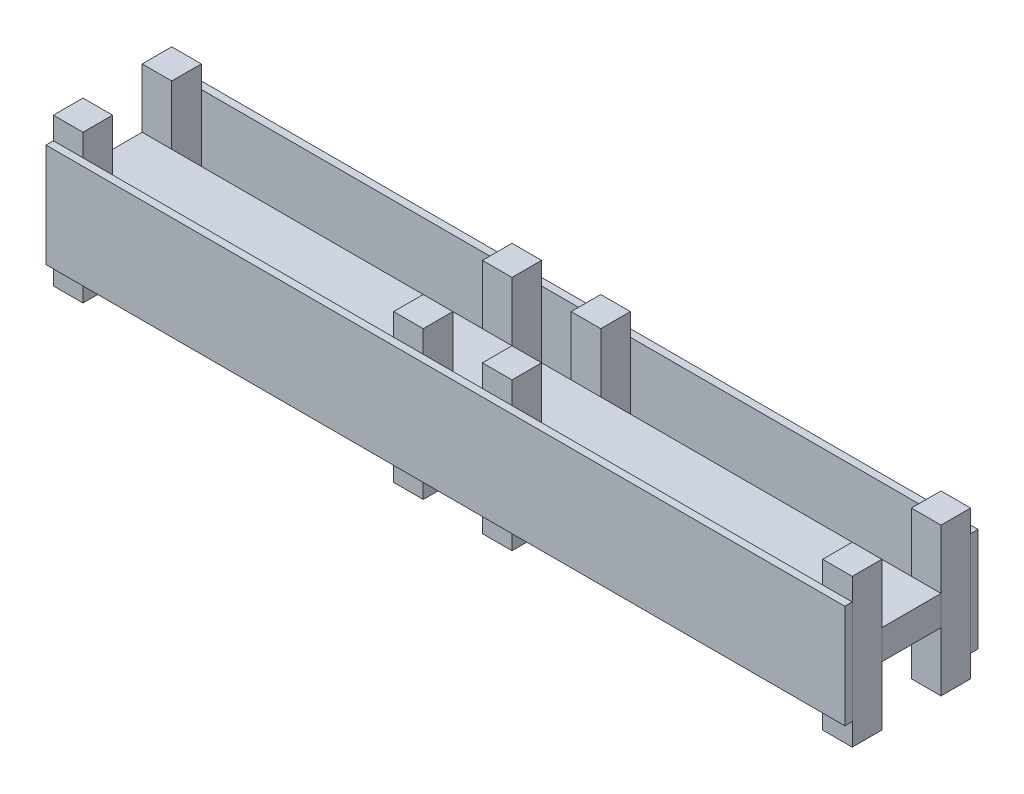
SolidWorks part; units mm, degrees
ref_plane "Front Plane" through (0, 0, 0) normal (0, 0, 1) x (1, 0, 0)
ref_plane "Top Plane" through (0, 0, 0) normal (0, 1, 0) x (1, 0, 0)
ref_plane "Right Plane" through (0, 0, 0) normal (1, 0, 0) x (0, 0, -1)
ref_plane "Plane1" through (0, 50, 0) normal (0, 1, 0) x (1, 0, 0)
sketch "Sketch2" plane through (0, 0, 0) normal (0, 1, 0) x (1, 0, 0)
  line L0 (270, 20) -> (-270, 20)
  line L1 (270, 20) -> (270, -20)
  line L2 (-270, 20) -> (-270, -20)
  line L3 (270, -20) -> (-270, -20)
  line L4 (270, 20) -> (-270, -20) construction
  line L5 (-270, 20) -> (270, -20) construction
  point P1 (0, 0)
  dimension "D1" = 40
extrude "Boss-Extrude2" add sketch "Sketch2" along normal blind 10 and the other way blind 10
sketch "Sketch3" plane through (0, 0, 0) normal (0, 1, 0) x (1, 0, 0)
  line L0 (-11, 0) -> (11, 0) construction
  line L6 (-250, -40) -> (-270, -40)
  line L7 (-250, -40) -> (-250, -20)
  line L8 (-250, -20) -> (-270, -20)
  line L9 (-270, -40) -> (-270, -20)
  line L21 (-40, -40) -> (-20, -40)
  line L22 (-40, -40) -> (-40, -20)
  line L23 (-40, -20) -> (-20, -20)
  line L24 (-20, -40) -> (-20, -20)
  line L42 (-20, 40) -> (-20, 20)
  line L43 (-40, 20) -> (-20, 20)
  line L44 (-40, 40) -> (-40, 20)
  line L45 (-40, 40) -> (-20, 40)
  line L46 (-270, 40) -> (-270, 20)
  line L47 (-250, 20) -> (-270, 20)
  line L48 (-250, 40) -> (-250, 20)
  line L49 (-250, 40) -> (-270, 40)
  line L50 (0, -11) -> (0, 11) construction
  line L51 (250, 40) -> (270, 40)
  line L52 (250, 40) -> (250, 20)
  line L53 (250, 20) -> (270, 20)
  line L54 (270, 40) -> (270, 20)
  line L55 (40, 40) -> (20, 40)
  line L56 (40, 40) -> (40, 20)
  line L57 (40, 20) -> (20, 20)
  line L58 (20, 40) -> (20, 20)
  line L59 (20, -40) -> (20, -20)
  line L60 (40, -20) -> (20, -20)
  line L61 (40, -40) -> (40, -20)
  line L62 (40, -40) -> (20, -40)
  line L63 (270, -40) -> (270, -20)
  line L64 (250, -20) -> (270, -20)
  line L65 (250, -40) -> (250, -20)
  line L66 (250, -40) -> (270, -40)
  point P5 (0, 0)
  point P6 (0, 0)
  point P12 (0, 0)
  point P13 (0, 0)
  point P19 (0, 0)
  point P20 (0, 0)
  point P26 (0, 0)
  point P27 (0, 0)
  point P33 (0, 0)
  point P34 (0, 0)
  point P45 (0, 0)
  point P52 (0, 0)
  point P53 (0, 0)
  point P54 (0, 0)
  point P55 (0, 0)
  point P56 (0, 0)
  dimension "D2" = 20
  dimension "D3" = 20
  dimension "D4" = 20
  dimension "D21" = 20
  dimension "D22" = 210
  dimension "D23" = 20
extrude "Boss-Extrude3" add sketch "Sketch3" along normal blind 50 and the other way blind 50 separate body
sketch "Sketch1" plane through (0, 50, 0) normal (0, 1, 0) x (1, 0, 0)
  line L0 (0, -33) -> (0, 33) construction
  line L1 (-270, 40) -> (270, 40) construction
  line L2 (-270, 40) -> (-270, -40) construction
  line L3 (-270, -40) -> (270, -40) construction
  line L4 (270, 40) -> (270, -40) construction
  line L5 (-270, 40) -> (270, -40) construction
  line L6 (-270, -40) -> (270, 40) construction
  line L7 (-270, 40) -> (-250, 40)
  line L8 (-270, 40) -> (-270, -40)
  line L9 (-270, -40) -> (-250, -40)
  line L10 (-250, 40) -> (-250, -40)
  line L11 (-40, 40) -> (-20, 40)
  line L12 (-40, 40) -> (-40, -40)
  line L13 (-40, -40) -> (-20, -40)
  line L14 (-20, 40) -> (-20, -40)
  line L15 (270, 40) -> (270, -40) construction
  line L16 (20, 40) -> (20, -40)
  line L17 (40, -40) -> (20, -40)
  line L18 (40, 40) -> (40, -40)
  line L19 (40, 40) -> (20, 40)
  line L20 (250, 40) -> (250, -40)
  line L21 (270, -40) -> (250, -40)
  line L22 (270, 40) -> (270, -40)
  line L23 (270, 40) -> (250, 40)
  point P0 (0, 0)
  dimension "D1" = 80
  dimension "D2" = 540
  dimension "D3" = 20
  dimension "D4" = 20
  dimension "D5" = 210
sketch "Sketch9" plane through (0, 0, 40) normal (0, 0, 1) x (1, 0, 0)
  line L0 (270, -50) -> (270, 50) construction
  line L1 (-270, 35) -> (270, 35)
  line L2 (-270, 35) -> (-270, -35)
  line L3 (-270, -35) -> (270, -35)
  line L4 (270, 35) -> (270, -35)
  line L5 (-270, 35) -> (270, -35) construction
  line L6 (-270, -35) -> (270, 35) construction
  point P0 (0, 0)
  dimension "D1" = 70
extrude "Boss-Extrude10" add sketch "Sketch9" along normal blind 5 separate body
sketch "Sketch10" plane through (0, 0, -40) normal (0, 0, -1) x (-1, 0, 0)
  line L0 (-270, 35) -> (270, 35) construction
  line L1 (-270, -35) -> (270, -35)
  line L2 (-270, -35) -> (-270, 35)
  line L3 (-270, 35) -> (270, 35)
  line L4 (270, -35) -> (270, 35)
  line L5 (-270, -35) -> (270, 35) construction
  line L6 (-270, 35) -> (270, -35) construction
  line L7 (270, -50) -> (270, 50) construction
  point P0 (0, 0)
extrude "Boss-Extrude11" add sketch "Sketch10" along normal blind 5 separate body
